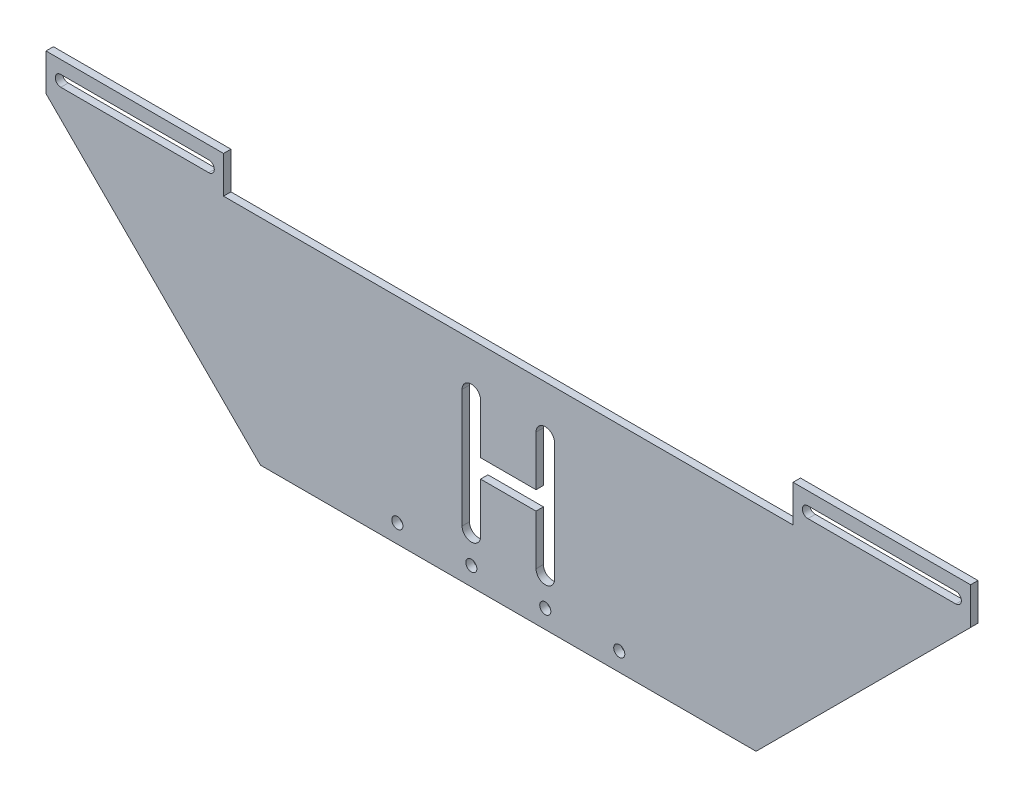
SolidWorks part; units mm, degrees
material "6061 合金"
ref_plane "前视基准面" through (0, 0, 0) normal (0, 0, 1) x (1, 0, 0)
ref_plane "上视基准面" through (0, 0, 0) normal (0, 1, 0) x (1, 0, 0)
ref_plane "右视基准面" through (0, 0, 0) normal (1, 0, 0) x (0, 0, -1)
sketch "草图1" plane through (0, 0, 0) normal (0, 0, 1) x (1, 0, 0)
  line L0 (-77, 30) -> (-77, 0)
  line L1 (-77, 0) -> (77, 0)
  line L2 (77, 0) -> (77, 30)
  line L3 (-77, 30) -> (-125, 30)
  line L5 (-67, -58) -> (67, -58)
  line L7 (125, 30) -> (77, 30)
  line L8 (0, 0) -> (0, -58) construction
  line L9 (-121, 25) -> (-81, 25) construction
  line L10 (-121, 25) -> (-121, 5) construction
  line L11 (-121, 5) -> (-81, 5) construction
  line L12 (-81, 25) -> (-81, 5) construction
  line L13 (81, 25) -> (81, 5) construction
  line L14 (121, 5) -> (81, 5) construction
  line L15 (121, 25) -> (121, 5) construction
  line L16 (121, 25) -> (81, 25) construction
  line L17 (-30, -53) -> (-10, -53) construction
  line L18 (30, -53) -> (10, -53) construction
  line L19 (-125, 30) -> (-125, 0)
  line L20 (-125, 0) -> (-67, -58)
  line L21 (67, -58) -> (125, 0)
  line L22 (125, 0) -> (125, 30)
  circle A0 centre (-121, 25) radius 1.5
  circle A1 centre (-81, 25) radius 1.5
  circle A2 centre (-81, 5) radius 1.5
  circle A3 centre (-121, 5) radius 1.5
  circle A4 centre (121, 5) radius 1.5
  circle A5 centre (81, 5) radius 1.5
  circle A6 centre (81, 25) radius 1.5
  circle A7 centre (121, 25) radius 1.5
  circle A8 centre (-30, -53) radius 1.5
  circle A9 centre (-10, -53) radius 1.5
  circle A10 centre (10, -53) radius 1.5
  circle A11 centre (30, -53) radius 1.5
  point P4 (0, 0)
  dimension "D5" = 3
  dimension "D10" = 3
  dimension "D1" = 30
  dimension "D2" = 154
  dimension "D3" = 58
  dimension "D4" = 48
  dimension "D6" = 5
  dimension "D7" = 5
  dimension "D8" = 4
  dimension "D9" = 4
  dimension "D11" = 20
  dimension "D12" = 10
  dimension "D13" = 5
  dimension "D14" = 45
extrude "凸台-拉伸1" add sketch "草图1" along normal blind 2 contours L21 A11 L22 L7 L2 L1 L0 L3 L19 L20 A8 L5 A7 A5 A0 A1 A2 A3 A4 A6 A9 A10 region at (0, -17.6995, 0)
sketch "草图8" plane through (0, 0, 2) normal (0, 0, 1) x (1, 0, 0)
  line L0 (-125, 30) -> (-125, 10)
  line L1 (-125, 30) -> (-125, 0) construction
  line L2 (-125, 10) -> (125, 10)
  line L3 (125, 0) -> (125, 30) construction
  line L4 (125, 10) -> (125, 30)
  line L5 (125, 30) -> (-125, 30)
extrude "切除-拉伸7" cut sketch "草图8" against normal blind 10
sketch "草图9" plane through (0, 0, 0) normal (0, 0, -1) x (-1, 0, 0)
  line L0 (-121, 5) -> (-81, 5)
  line L1 (81, 5) -> (121, 5)
  line L2 (-121, 5) -> (-81, 5) construction
  line L3 (-121, 6.5) -> (-81, 6.5)
  line L4 (-121, 3.5) -> (-81, 3.5)
  line L5 (81, 5) -> (121, 5) construction
  line L6 (81, 6.5) -> (121, 6.5)
  line L7 (81, 3.5) -> (121, 3.5)
  arc A0 (-121, 6.5) -> (-121, 3.5) centre (-121, 5) ccw
  arc A1 (-81, 3.5) -> (-81, 6.5) centre (-81, 5) ccw
  arc A2 (81, 6.5) -> (81, 3.5) centre (81, 5) ccw
  arc A3 (121, 3.5) -> (121, 6.5) centre (121, 5) ccw
  point P8 (-101, 5)
  point P13 (101, 5)
  circle M4 centre (-121, 5) radius 1.5
  circle M5 centre (121, 5) radius 1.5
  circle M6 centre (81, 5) radius 1.5
  circle M17 centre (-81, 5) radius 1.5
extrude "切除-拉伸8" cut sketch "草图9" against normal blind 10 contours L7 L1 M6 M5 | L6 L1 M6 M5 | L4 L0 M4 M17 | L3 L0 M4 M17 region at (101, 5.7571, 0) region at (101, 4.2429, 0) region at (-101, 5.7571, 0) region at (-101, 4.2429, 0)
sketch "草图10" plane through (0, 0, 0) normal (0, 0, -1) x (-1, 0, 0)
  line L0 (0, 0) -> (0, -58)
  line L1 (67, -58) -> (-67, -58) construction
  line L2 (0, -29) -> (-10, -29)
  line L3 (0, -29) -> (10, -29)
  line L4 (-10, -29) -> (-10, -45)
  line L5 (-10, -29) -> (-10, -13)
  line L6 (10, -29) -> (10, -13)
  line L7 (10, -29) -> (10, -45)
  line L8 (-10, -13) -> (-10, -45) construction
  line L9 (-7.5, -13) -> (-7.5, -26.5)
  line L10 (-12.5, -13) -> (-12.5, -45)
  line L11 (-10, -29) -> (10, -29) construction
  line L12 (-7.5, -26.5) -> (7.5, -26.5)
  line L13 (-7.5, -31.5) -> (7.5, -31.5)
  line L14 (10, -13) -> (10, -45) construction
  line L15 (12.5, -13) -> (12.5, -45)
  line L16 (7.5, -13) -> (7.5, -26.5)
  line L17 (7.5, -31.5) -> (7.5, -45)
  line L18 (-7.5, -31.5) -> (-7.5, -45)
  arc A0 (-7.5, -13) -> (-12.5, -13) centre (-10, -13) ccw
  arc A1 (-12.5, -45) -> (-7.5, -45) centre (-10, -45) ccw
  arc A4 (12.5, -13) -> (7.5, -13) centre (10, -13) ccw
  arc A5 (7.5, -45) -> (12.5, -45) centre (10, -45) ccw
  point P7 (-10, -29)
  point P17 (0, -29)
  point P22 (10, -29)
  dimension "D1" = 16
  dimension "D2" = 10
  dimension "D3" = 10
extrude "切除-拉伸9" cut sketch "草图10" against normal blind 10 contours L10 A1 L18 L13 L0 L12 L9 A0 | L17 A5 L15 A4 L16 L12 L0 L13 region at (-3.75, -26.8905, 0) region at (0.3905, -27.75, 0)
